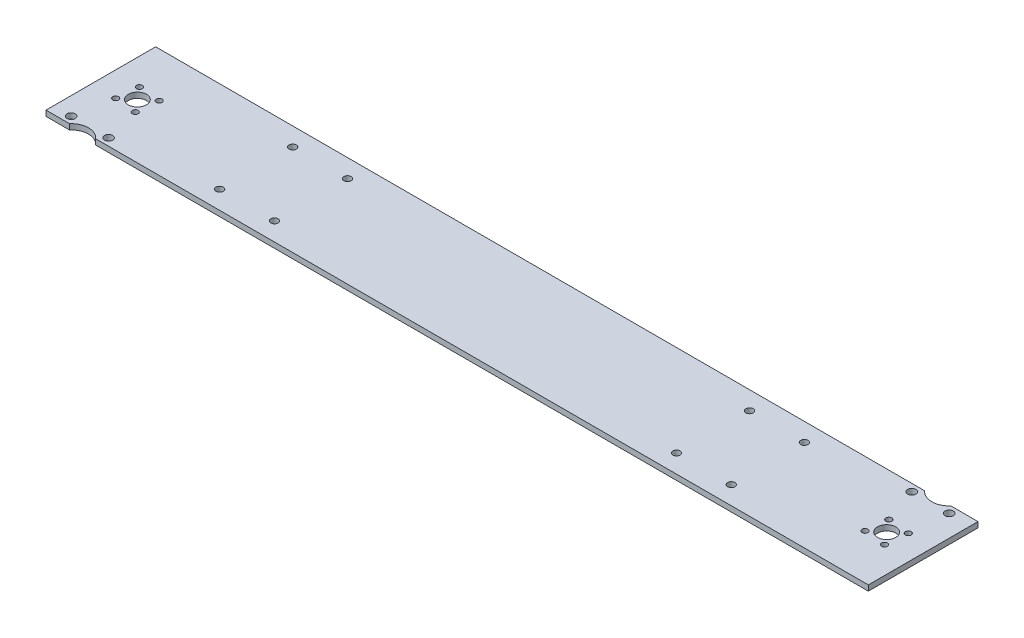
SolidWorks part; units mm, degrees
material "3.0515 (EN-AW 3103)"
ref_plane "Płaszczyzna przednia" through (0, 0, 0) normal (0, 0, 1) x (1, 0, 0)
ref_plane "Płaszczyzna górna" through (0, 0, 0) normal (0, 1, 0) x (1, 0, 0)
ref_plane "Płaszczyzna prawa" through (0, 0, 0) normal (1, 0, 0) x (0, 0, -1)
sketch "Szkic1" plane through (0, 0, 0) normal (0, 1, 0) x (1, 0, 0)
  line L1 (0, 0) -> (-450, 0)
  line L2 (0, 0) -> (0, 60)
  line L3 (0, 60) -> (-450, 60)
  line L4 (-450, 0) -> (-450, 60)
  dimension "D1" = 60
  dimension "D2" = 450
extrude "Dodanie-wyciągnięcie1" add sketch "Szkic1" along normal blind 3
hole_wizard "Otwór pod śrubę M41" positions "Szkic6" profile "Szkic7" hole size "M4" standard "Ansi Metric" end condition through all
sketch "Szkic6" plane through (0, 3, 0) normal (0, 1, 0) x (1, 0, 0)
  line L0 (0, 60) -> (-450, 60) construction
  line L1 (-450, 0) -> (0, 0) construction
  line L2 (-450, 60) -> (-450, 0) construction
  line L3 (0, 0) -> (0, 60) construction
  point P0 (-365, 50)
  point P2 (-335, 50)
  point P4 (-365, 10)
  point P6 (-335, 10)
  point P8 (-115, 50)
  point P10 (-85, 50)
  point P12 (-115, 10)
  point P14 (-85, 10)
  dimension "D1" = 10
  dimension "D2" = 10
  dimension "D3" = 30
  dimension "D4" = 30
  dimension "D5" = 30
  dimension "D6" = 30
  dimension "D7" = 85
  dimension "D8" = 85
  dimension "D9" = 85
  dimension "D10" = 85
sketch "Szkic7" plane through (-365, 3, -50) normal (1, 0, 0) x (0, 0, 1)
  line L0 (0, 0) -> (0, 3)
  line L1 (0, 3) -> (2, 3)
  line L2 (2, 3) -> (2, 0)
  line L5 (2, 0) -> (0, 0)
  line L11 (0, -6.35) -> (0, 107.95) construction
  dimension "Œrednica otworu na wylot" = 4
  dimension "G³êbokoœæ otworu na wylot" = 3
sketch "Szkic8" plane through (0, 3, 0) normal (0, 1, 0) x (1, 0, 0)
  line L0 (0, 60) -> (-450, 60) construction
  line L2 (0, 0) -> (0, 60) construction
  line L3 (-450, 60) -> (-450, 0) construction
  circle A0 centre (-20, 30) radius 5
  circle A1 centre (-430, 30) radius 5
  dimension "D1" = 10
  dimension "D2" = 30
  dimension "D3" = 20
  dimension "D4" = 10
  dimension "D5" = 30
  dimension "D6" = 20
extrude "Wytnij-wyciągnięcie1" cut sketch "Szkic8" against normal blind 10
sketch "Szkic9" plane through (0, 3, 0) normal (0, 1, 0) x (1, 0, 0)
  circle A0 centre (-435.3563, 36.5109) radius 1.6
  circle A1 centre (-436.5109, 24.6437) radius 1.6
  circle A2 centre (-424.6437, 23.4891) radius 1.6
  circle A3 centre (-423.4891, 35.3563) radius 1.6
extrude "Wytnij-wyciągnięcie2" cut sketch "Szkic9" against normal through all
sketch "Szkic10" plane through (0, 3, 0) normal (0, 1, 0) x (1, 0, 0)
  circle A0 centre (-13.4891, 35.3563) radius 1.6
  circle A1 centre (-14.6437, 23.4891) radius 1.6
  circle A2 centre (-26.5109, 24.6437) radius 1.6
  circle A4 centre (-25.3457, 36.555) radius 1.6
  dimension "D1" = 3.2
extrude "Wytnij-wyciągnięcie3" cut sketch "Szkic10" against normal blind 10
sketch "Sketch1" plane through (0, 3, 0) normal (0, 1, 0) x (1, 0, 0)
  line L0 (-430, 30) -> (-430, 0) construction
  line L1 (-450, 0) -> (0, 0) construction
  line L2 (-444.5, -6.253) -> (-430, 8.247) construction
  line L3 (-437.25, 0.997) -> (-445.2636, 9.0105) construction
  line L4 (-226.0073, 60) -> (-226.0073, 0) construction
  line L5 (0, 60) -> (-450, 60) construction
  line L6 (-450, 30) -> (0, 30) construction
  line L7 (-450, 60) -> (-450, 0) construction
  line L8 (0, 0) -> (0, 60) construction
  circle A1 centre (-430, -6.253) radius 9.5
  circle A2 centre (-430, -6.253) radius 14.5 construction
  circle A5 centre (-440.253, 4) radius 2.25
  circle A6 centre (-419.747, 4) radius 2.25
  circle A10 centre (-11.7616, 56) radius 2.25
  circle A11 centre (-32.2677, 56) radius 2.25
  circle A12 centre (-22.0146, 66.253) radius 9.5
  point P12 (-440.253, 4)
  dimension "D1" = 19
  dimension "D2" = 29
  dimension "D3" = 4.5
  dimension "D4" = 4
extrude "Cut-Extrude1" cut sketch "Sketch1" against normal through all
ref_plane "Plane1" through (-225, 0, 0) normal (1, 0, 0) x (0, 0, -1)
